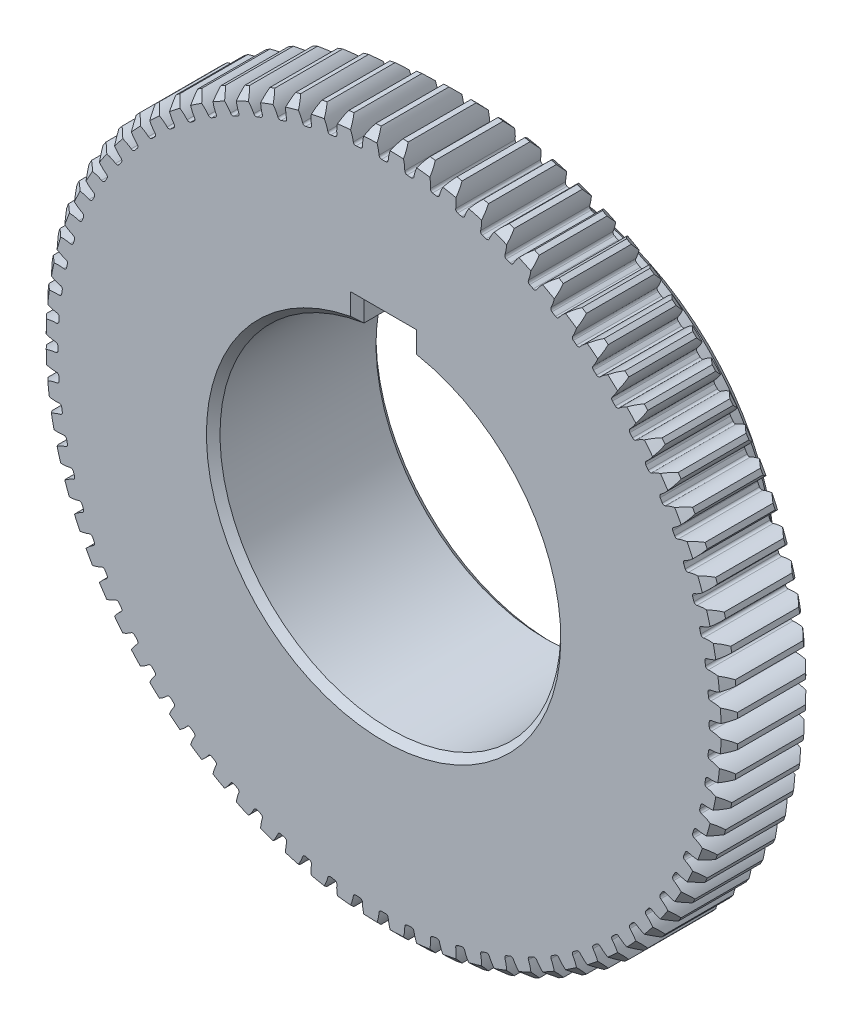
SolidWorks part; units mm, degrees
material "Plain Carbon Steel"
ref_plane "Front Plane" through (0, 0, 0) normal (0, 0, 1) x (1, 0, 0)
ref_plane "Top Plane" through (0, 0, 0) normal (0, 1, 0) x (1, 0, 0)
ref_plane "Right Plane" through (0, 0, 0) normal (1, 0, 0) x (0, 0, -1)
sketch "Sketch2" plane through (0, 0, 0) normal (0, 0, 1) x (1, 0, 0)
  circle A0 centre (0, 0) radius 39.8
  circle A1 centre (0, 0) radius 40.795
  circle A2 centre (0, 0) radius 38.407
  dimension "D1" = 79.6
  dimension "D2" = 81.59
  dimension "D3" = 2.388
extrude "Boss-Extrude1" add sketch "Sketch2" along normal mid plane 10 contours A1
sketch "Sketch3" plane through (0, 0, 0) normal (0, 0, 1) x (1, 0, 0)
  line L0 (0, 0) -> (0, 40.795) construction
  line L1 (-0.7814, 39.7923) -> (0.7814, 39.7923) construction
  line L2 (-0.5267, 38.4034) -> (0, 0) construction
  line L3 (0, 37.6454) -> (-1.5005, 41.7681) construction
  line L4 (0, 0) -> (1.6016, 40.7635) construction
  line L5 (0.7814, 39.7923) -> (2.3431, 39.731) construction
  circle A0 centre (0, 0) radius 40.795 construction
  arc A1 (-2.2263, 41.7357) -> (-0.5267, 38.4034) centre (-4.7569, 38.3454) cw
  arc A2 (2.2263, 41.7357) -> (0.5267, 38.4034) centre (4.7569, 38.3454) ccw
  circle A3 centre (0, 0) radius 38.407 construction
  arc A4 (0.5267, 38.4034) -> (-0.5267, 38.4034) centre (0, 0) ccw
  circle A6 centre (0, 0) radius 39.8 construction
  circle A7 centre (0, 0) radius 41.795
  arc A8 (2.2263, 41.7357) -> (-2.2263, 41.7357) centre (0, 0) ccw
  circle A9 centre (0, 0) radius 40.795 construction
  dimension "D2" = 20
  dimension "D3" = 2.25
extrude "Cut-Extrude1" cut sketch "Sketch3" against normal through all both and the other way through all
fillet "Fillet1" radius 0.2985 2 edges at (0.5267, 38.4034, 0) (-0.5267, 38.4034, 0)
chamfer "Chamfer1" distance 0.995 2 edges at (0, -40.795, -5) (0, -40.795, 5)
pattern_circular "CirPattern1" count 80 over 360 about axis through (0, 0, 0) along (0, 0, 1) of "Fillet1", "Cut-Extrude1"
sketch "Sketch5" plane through (0, 0, -5) normal (0, 0, -1) x (-1, 0, 0)
  circle A5 centre (0, 0) radius 27
  dimension "D1" = 54
extrude "Boss-Extrude2" add sketch "Sketch5" along normal blind 10
sketch "Sketch6" plane through (0, 0, -15) normal (0, 0, 1) x (1, 0, 0)
  circle A1 centre (0, 0) radius 20.1
  circle A2 centre (0, 0) radius 27 construction
  dimension "D1" = 40.2
extrude "Cut-Extrude3" cut sketch "Sketch6" along normal blind 40
sketch "Sketch7" plane through (0, 0, -15) normal (0, 0, -1) x (-1, 0, 0)
  line L0 (0, -1000) -> (0, 49000) construction
  line L5 (-3.1, 22.2595) -> (3.1, 22.2595)
  line L6 (-3.1, 22.2595) -> (-3.1, 19.8595)
  line L7 (-3.1, 19.8595) -> (3.1, 19.8595)
  line L8 (3.1, 22.2595) -> (3.1, 19.8595)
  line L9 (-3.1, 22.2595) -> (3.1, 19.8595) construction
  line L10 (-3.1, 19.8595) -> (3.1, 22.2595) construction
  circle A3 centre (0, 0) radius 20.1 construction
  point P1 (0, 21.0595)
  dimension "D1" = 2.4
  dimension "D2" = 6.2
extrude "Cut-Extrude4" cut sketch "Sketch7" against normal through all
chamfer "Chamfer2" distance 0.8 angle 45 9 edges at (3.1, 21.0595, -15) (0, 22.2595, -15) (-3.1, 21.0595, -15) (0, -20.1, -15) (3.1, 21.0595, 5) (0, 22.2595, 5) (-3.1, 21.0595, 5) (0, -20.1, 5) (-27, 0, -15)
chamfer "Chamfer3" distance 2 angle 45 1 edges at (27, 0, -5)
equation "\"Module\" = 0.995mm"
equation "\"Number of Teeth\"= 80"
equation "\"D1@Sketch2\"=\"Module\" * \"Number of Teeth\""
equation "\"D2@Sketch2\"=(\"Number of Teeth\" + 2) * \"Module\""
equation "\"D3@Sketch2\"=\"Module\" * if( \"Module\" => 1.25, 2.25, 2.4) "
equation "\"D3@Sketch3\"=180deg / \"Number of Teeth\""
equation "\"D1@Fillet1\"=0.3 * \"Module\""
equation "\"D1@CirPattern1\"=\"Number of Teeth\""
equation "\"D1@Chamfer1\"=\"Module\""
equation "\"Pressure Angle\"= 20deg"
equation "\"D2@Sketch3\"=\"Pressure Angle\""
